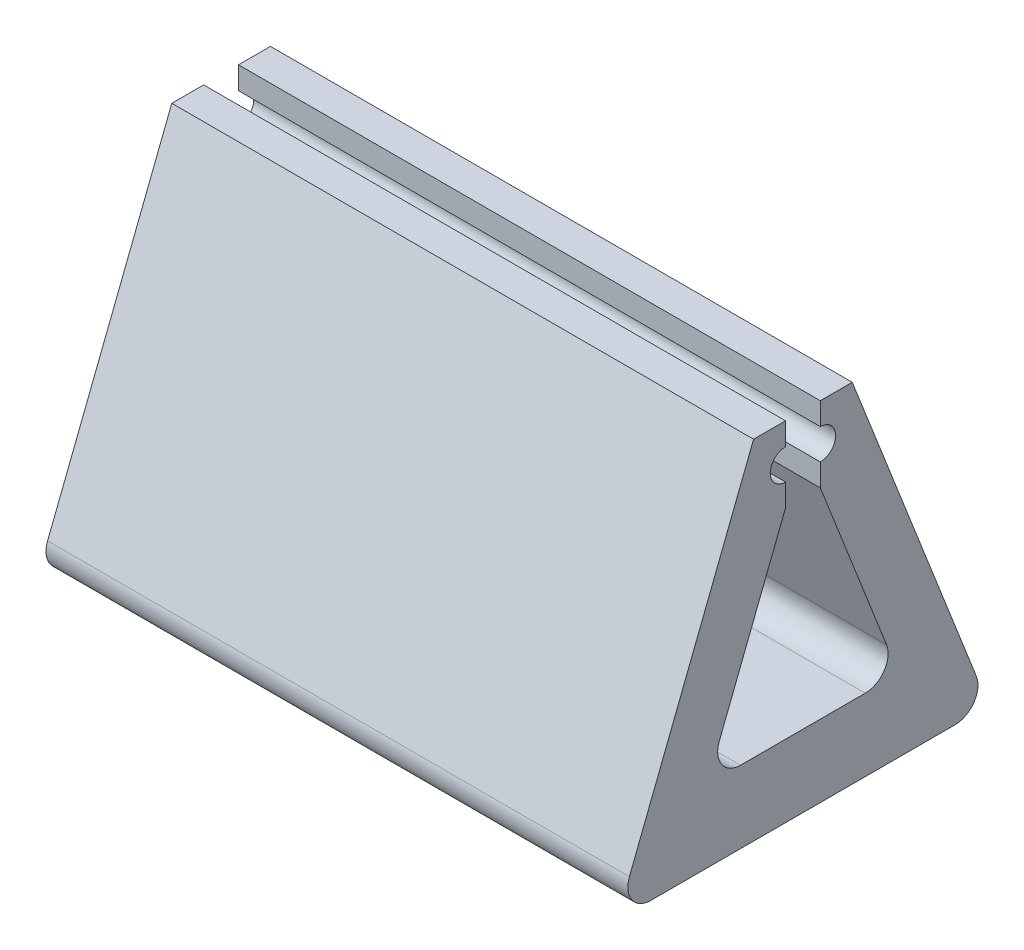
SolidWorks part; units mm, degrees
ref_plane "Front Plane" through (0, 0, 0) normal (0, 0, 1) x (1, 0, 0)
ref_plane "Top Plane" through (0, 0, 0) normal (0, 1, 0) x (1, 0, 0)
ref_plane "Right Plane" through (0, 0, 0) normal (1, 0, 0) x (0, 0, -1)
sketch "Sketch1" plane through (0, 0, 0) normal (1, 0, 0) x (0, 0, -1)
  line L0 (-0.456, 7.2236) -> (-0.456, 5.2461)
  line L1 (-1.633, 0) -> (1.633, 0)
  line L2 (0.456, 5.2461) -> (2.1916, 0.819)
  line L3 (0.456, 7.2236) -> (1.2919, 7.2236)
  line L4 (1.2919, 7.2236) -> (4.5453, -1.0748)
  line L5 (3.9867, -1.8938) -> (-3.9867, -1.8938)
  line L6 (-4.5453, -1.0748) -> (-1.2919, 7.2236)
  line L7 (-1.2919, 7.2236) -> (-0.456, 7.2236)
  line L8 (0, 0) -> (0, 50000) construction
  line L9 (-0.456, 5.2461) -> (-2.1916, 0.819)
  line L10 (0.456, 7.2236) -> (0.456, 5.2461)
  arc A0 (-2.1916, 0.819) -> (-1.633, 0) centre (-1.633, 0.6) ccw
  arc A1 (1.633, 0) -> (2.1916, 0.819) centre (1.633, 0.6) ccw
  arc A2 (-3.9867, -1.8938) -> (-4.5453, -1.0748) centre (-3.9867, -1.2938) cw
  arc A3 (3.9867, -1.8938) -> (4.5453, -1.0748) centre (3.9867, -1.2938) ccw
  arc A4 (-0.456, 5.8349) -> (-0.456, 6.6349) centre (-0.456, 6.2349) cw
  arc A5 (0.456, 5.8349) -> (0.456, 6.6349) centre (0.456, 6.2349) ccw
  point P26 (0, -1.8938)
  dimension "D2" = 0.6
  dimension "D4" = 0.6
  dimension "D6" = 0.4
  dimension "D1" = 0.912
  dimension "D7" = 1.5
extrude "Boss-Extrude1" add sketch "Sketch1" along normal blind 15.24 contours L5 L8 L1 A0 L0 A4 L7 L6 A2 | L8 L5 A3 L4 L3 A5 A1 L1 region at (0, 6.9292, 0.5853)
